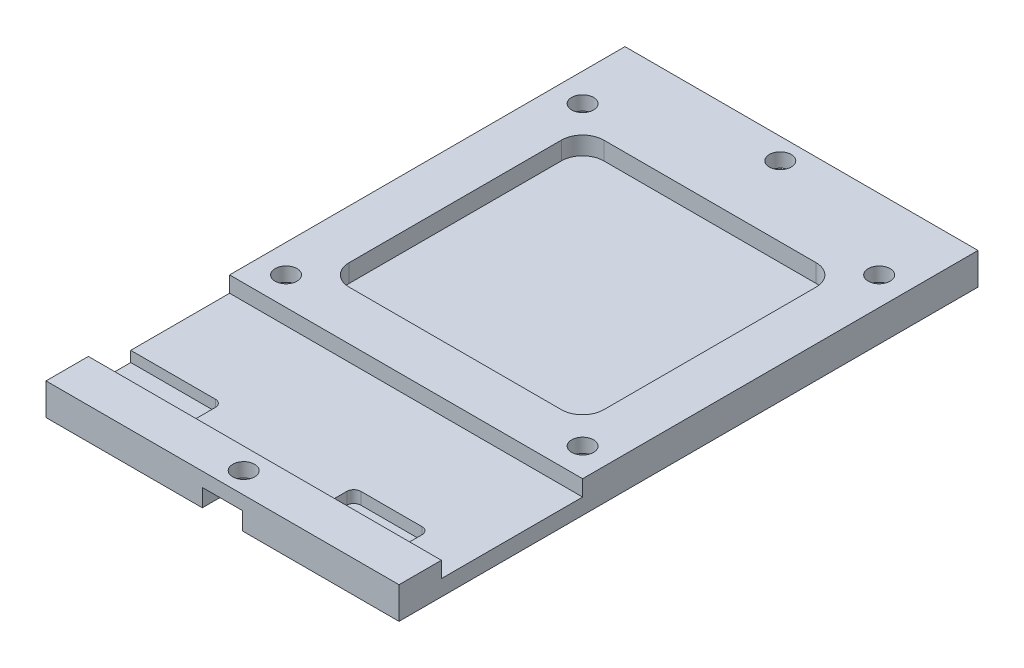
SolidWorks part; units mm, degrees
ref_plane "Спереди" through (0, 0, 0) normal (0, 0, 1) x (1, 0, 0)
ref_plane "Сверху" through (0, 0, 0) normal (0, 1, 0) x (1, 0, 0)
ref_plane "Справа" through (0, 0, 0) normal (1, 0, 0) x (0, 0, -1)
sketch "Основание" plane through (0, 0, 0) normal (0, 1, 0) x (1, 0, 0)
  line L1 (-25, -51) -> (25, -51)
  line L2 (-25, -51) -> (-25, 31)
  line L3 (-25, 31) -> (25, 31)
  line L4 (25, -51) -> (25, 31)
  dimension "D1" = 50
  dimension "D2" = 82
  dimension "D3" = 31
  dimension "D4" = 25
extrude "Бобышка-Вытянуть1" add sketch "Основание" along normal blind 5
sketch "Эскиз2" plane through (0, 5, 0) normal (0, 1, 0) x (1, 0, 0)
  line L5 (-18.035, -18.035) -> (18.035, -18.035)
  line L6 (-18.035, -18.035) -> (-18.035, 18.035)
  line L7 (-18.035, 18.035) -> (18.035, 18.035)
  line L8 (18.035, -18.035) -> (18.035, 18.035)
  line L9 (-18.035, -18.035) -> (18.035, 18.035) construction
  line L10 (-18.035, 18.035) -> (18.035, -18.035) construction
  point P4 (0, 0)
  dimension "D1" = 36.07
extrude "Выемка для ADR1399KEZ" cut sketch "Эскиз2" against normal blind 2.55
sketch "Эскиз3" plane through (0, 0, 0) normal (0, 1, 0) x (1, 0, 0)
  line L0 (0, 0) -> (33.2111, 0) construction
  line L1 (0, 10.0667) -> (0, -12.5959) construction
  circle A0 centre (-21, 21) radius 1.55
  circle A1 centre (21, 21) radius 1.55
  circle A2 centre (-21, -21) radius 1.55
  circle A3 centre (21, -21) radius 1.55
  circle A4 centre (0, 28) radius 1.55
  circle A5 centre (0, -48) radius 1.55
  dimension "D1" = 3.1
  dimension "D2" = 21
  dimension "D3" = 21
  dimension "D4" = 28
  dimension "D5" = 48
extrude "Крепежныые винты и внешние вырезы" cut sketch "Эскиз3" along direction (0, -1, 0) on the side of the normal through all from surface starting at face at (0, 0, 10)
sketch "Эскиз5" plane through (0, 5, 0) normal (0, 1, 0) x (1, 0, 0)
  line L0 (25, -51) -> (25, 31) construction
  line L1 (-25, -45) -> (25, -45)
  line L2 (-25, -45) -> (-25, -25)
  line L3 (-25, -25) -> (25, -25)
  line L4 (25, -45) -> (25, -25)
  line L6 (-25, -51) -> (25, -51) construction
  line L9 (-25, 31) -> (-25, -51) construction
  dimension "D1" = 25
  dimension "D2" = 6
extrude "Выемка под компоненты" cut sketch "Эскиз5" against normal blind 2.25
fillet "Скругление под фрезу" radius 3 4 edges at (18.035, 3.725, 18.035) (-18.035, 3.725, 18.035) (-18.035, 3.725, -18.035) (18.035, 3.725, -18.035)
sketch "Эскиз6" plane through (0, 0, 0) normal (0, -1, 0) x (1, 0, 0)
  circle A0 centre (-21, -21) radius 2.86
  circle A1 centre (-21, 21) radius 2.86
  circle A2 centre (21, 21) radius 2.86
  circle A3 centre (21, -21) radius 2.86
  circle A4 centre (0, 48) radius 2.86
  circle A5 centre (0, -28) radius 2.86
  dimension "D1" = 5.72
extrude "Потай головок винтов" cut sketch "Эскиз6" against normal blind 3
sketch "Эскиз7" plane through (0, 0, 0) normal (0, -1, 0) x (1, 0, 0)
  line L1 (-25, 51) -> (25, 51) construction
  line L11 (-25, -31) -> (-25, 51) construction
  line L12 (-25, 39) -> (-12, 39)
  line L13 (-25, 39) -> (-25, 45)
  line L14 (-25, 45) -> (-12, 45)
  line L15 (-12, 39) -> (-12, 45)
  dimension "D5" = 6
  dimension "D6" = 6
  dimension "D7" = 13
extrude "Вырез-Вытянуть7" cut sketch "Эскиз7" along normal blind 1.5 from surface starting at face at (0, 2.75, 35)
fillet "Скругление2" radius 1 2 edges at (-12, 2, 39) (-12, 2, 45)
sketch "Эскиз8" plane through (0, 0, 0) normal (0, -1, 0) x (1, 0, 0)
  line L0 (11.5373, 51) -> (11.5373, -31) construction
  line L1 (3.626, 51) -> (3.626, -31) construction
  line L2 (25, -31) -> (-25, -31) construction
  line L3 (-25, 51) -> (25, 51) construction
  line L4 (-14.969, 51) -> (-14.969, -31) construction
  text T0 "QUAD ADR1399K"
  text T1 "LOW NOISE VOLTAGE REFERENCE" font "Arial" height 3
  text T2 "(c) http://ampnuts.ru   \r\n" font "Arial" height 3
extrude "Вырез-Вытянуть8" cut sketch "Эскиз8" against normal blind 0.2
sketch "Эскиз10" plane through (0, 2.75, 0) normal (0, 1, 0) x (1, 0, 0)
  line L0 (25, -45) -> (25, -25) construction
  line L1 (7.6, -40) -> (18.25, -40)
  line L2 (7.6, -40) -> (7.6, -45)
  line L3 (7.6, -45) -> (18.25, -45)
  line L4 (18.25, -40) -> (18.25, -45)
  line L5 (-25, -51) -> (25, -51) construction
  dimension "D1" = 17.4
  dimension "D2" = 6.75
  dimension "D3" = 5
  dimension "D4" = 6
extrude "Вырез-Вытянуть10" cut sketch "Эскиз10" against normal blind 1.7
fillet "Скругление3" radius 1 4 edges at (7.6, 1.9, 45) (7.6, 1.9, 40) (18.25, 1.9, 40) (18.25, 1.9, 45)
sketch "Эскиз11" plane through (0, 0, 0) normal (0, -1, 0) x (1, 0, 0)
  line L0 (-25, 51) -> (25, 51) construction
  line L1 (2.86, 48) -> (-2.86, 48)
  line L2 (2.86, 48) -> (2.86, 51)
  line L3 (2.86, 51) -> (-2.86, 51)
  line L4 (-2.86, 48) -> (-2.86, 51)
  line L6 (2.86, -28) -> (-2.86, -28)
  line L7 (2.86, -28) -> (2.86, -31.0636)
  line L8 (2.86, -31.0636) -> (-2.86, -31.0636)
  line L9 (-2.86, -28) -> (-2.86, -31.0636)
  circle A0 centre (0, 48) radius 2.86 construction
  circle A1 centre (0, 48) radius 2.86 construction
  circle A2 centre (0, -28) radius 2.86 construction
  circle A3 centre (0, -28) radius 2.86 construction
extrude "Вырез-Вытянуть11" cut sketch "Эскиз11" against normal blind 3
chamfer "Фаска1" distance 0.5 angle 45 16 edges at (-21, 0, -23.86) (0, 0, -25.14) (21, 0, -23.86) (21, 0, 18.14) (-21, 0, 18.14) (0, 0, 45.14) (13.93, 0, 51) (-13.93, 0, 51) (-25, 0, 10) (13.93, 0, -31) (-13.93, 0, -31) (25, 0, 10) (2.86, 0, -29.5) (-2.86, 0, -29.5) (-2.86, 0, 49.5) (2.86, 0, 49.5)
